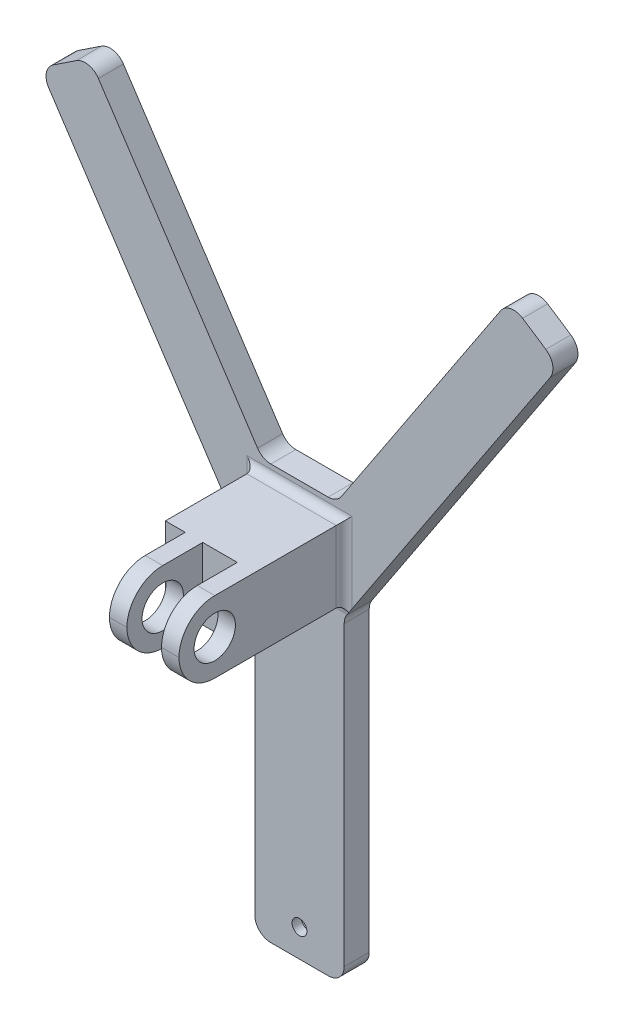
SolidWorks part; units mm, degrees
ref_plane "Plan de face" through (0, 0, 0) normal (0, 0, 1) x (1, 0, 0)
ref_plane "Plan de dessus" through (0, 0, 0) normal (0, 1, 0) x (1, 0, 0)
ref_plane "Plan de droite" through (0, 0, 0) normal (1, 0, 0) x (0, 0, -1)
sketch "Sketch1" plane through (0, 0, 0) normal (0, 0, 1) x (1, 0, 0)
  line L18 (-11.895, 65.5892) -> (11.895, 65.5892)
  line L19 (11.895, 65.5892) -> (67.0848, 148.9804)
  line L20 (67.0848, 148.9804) -> (82.9708, 138.4667)
  line L21 (82.9708, 138.4667) -> (14.2875, 34.687)
  line L23 (14.2875, 34.687) -> (14.2875, -66.913)
  line L24 (14.2875, -66.913) -> (-14.2875, -66.913)
  line L25 (-14.2875, -66.913) -> (-14.2875, 34.687)
  line L26 (-14.2875, 34.687) -> (-82.9708, 138.4667)
  line L27 (-82.9708, 138.4667) -> (-67.0848, 148.9804)
  line L28 (-67.0848, 148.9804) -> (-11.895, 65.5892)
  line L29 (-14.2875, 34.687) -> (14.2875, 34.687) construction
  point P2 (0, 34.687)
  point P12 (0, 65.5892)
  dimension "D1" = 28.575
  dimension "D2" = 19.05
  dimension "D3" = 100
  dimension "D4" = 100
  dimension "D5" = 101.6
extrude "Boss-Extrude1" add sketch "Sketch1" along normal blind 8
sketch "Sketch3" plane through (0, 0, 8) normal (0, 0, 1) x (1, 0, 0)
  line L0 (0, 65.5892) -> (0, 34.687) construction
  line L5 (14.2875, 38.7081) -> (-14.2875, 38.7081)
  line L6 (14.2875, 38.7081) -> (14.2875, 61.5681)
  line L7 (14.2875, 61.5681) -> (-14.2875, 61.5681)
  line L8 (-14.2875, 38.7081) -> (-14.2875, 61.5681)
  line L9 (14.2875, 38.7081) -> (-14.2875, 61.5681) construction
  line L10 (14.2875, 61.5681) -> (-14.2875, 38.7081) construction
  line L12 (11.895, 65.5892) -> (-11.895, 65.5892) construction
  point P0 (0, 50.1381)
  point P15 (0, 50.1381)
  dimension "D1" = 28.575
  dimension "D2" = 22.86
extrude "Boss-Extrude2" add sketch "Sketch3" along normal blind 52.8
sketch "Sketch6" plane through (0, 0, 8) normal (0, 0, 1) x (1, 0, 0)
  line L6 (-14.2875, 34.687) -> (-14.2875, -66.913) construction
  line L11 (-14.2875, 38.7081) -> (14.2875, 38.7081)
  line L12 (-14.2875, 38.7081) -> (-14.2875, -66.913)
  line L13 (-14.2875, -66.913) -> (14.2875, -66.913)
  line L14 (14.2875, 38.7081) -> (14.2875, -66.913)
  line L15 (-14.2875, -66.913) -> (14.2875, -66.913) construction
  line L16 (14.2875, -66.913) -> (14.2875, 34.687) construction
  line L17 (-14.2875, 38.7081) -> (14.2875, 38.7081) construction
extrude "Boss-Extrude3" [suppressed] add sketch "Sketch6" along normal blind 5.08
fillet "Fillet1" radius 5.08 10 edges at (-14.2875, -66.913, 4) (14.2875, -66.913, 4) (82.9708, 138.4667, 4) (67.0848, 148.9804, 4) (-67.0848, 148.9804, 4) (-82.9708, 138.4667, 4) (-11.895, 65.5892, 4) (11.895, 65.5892, 4) (14.2875, 34.687, 4) (-14.2875, 34.687, 4)
sketch "Sketch4" plane through (0, 38.7081, 0) normal (0, -1, 0) x (1, 0, 0)
  line L0 (-14.2875, 60.8) -> (14.2875, 60.8) construction
  line L1 (-14.2875, 60.8) -> (-7.9375, 60.8)
  line L2 (-14.2875, 60.8) -> (-14.2875, 36.575)
  line L3 (-14.2875, 36.575) -> (-7.9375, 36.575)
  line L4 (-7.9375, 60.8) -> (-7.9375, 36.575)
  line L5 (-2.3495, 60.8) -> (8.6995, 60.8)
  line L6 (-2.3495, 60.8) -> (-2.3495, 36.575)
  line L7 (-2.3495, 36.575) -> (8.6995, 36.575)
  line L8 (8.6995, 60.8) -> (8.6995, 36.575)
  line L9 (14.2875, 60.8) -> (14.2875, 8) construction
  dimension "D1" = 5.588
  dimension "D2" = 5.588
  dimension "D3" = 24.225
  dimension "D4" = 24.225
  dimension "D5" = 6.35
extrude "Cut-Extrude1" cut sketch "Sketch4" against normal through all
fillet "Fillet3" radius 11.43 4 edges at (11.4935, 61.5681, 60.8) (-5.1435, 61.5681, 60.8) (11.4935, 38.7081, 60.8) (-5.1435, 38.7081, 60.8)
sketch "Sketch5" plane through (-7.9375, 0, 0) normal (-1, 0, 0) x (0, 0, 1)
  circle A0 centre (49.37, 50.1381) radius 6.604
  dimension "D1" = 13.208
extrude "Cut-Extrude2" cut sketch "Sketch5" against normal through all
fillet "Fillet6" [suppressed] radius 2.54
sketch "Sketch7" plane through (0, 0, 0) normal (0, 0, -1) x (-1, 0, 0)
  line L0 (9.2075, -66.913) -> (-9.2075, -66.913) construction
  line L1 (14.2875, 33.1582) -> (14.2875, -61.833) construction
  circle A0 centre (0, -58.023) radius 4.2333
  dimension "D1" = 8.4667
  dimension "D2" = 8.89
  dimension "D3" = 14.2875
extrude "Cut-Extrude3" cut sketch "Sketch7" against normal blind 5.08
sketch "Sketch8" plane through (0, 0, 5.08) normal (0, 0, -1) x (-1, 0, 0)
  line L0 (14.2875, 33.1582) -> (14.2875, -61.833) construction
  line L2 (9.2075, -66.913) -> (-9.2075, -66.913) construction
  circle A0 centre (0, -58.023) radius 2.3812
  dimension "D1" = 4.7625
  dimension "D2" = 14.2875
  dimension "D3" = 8.89
extrude "Cut-Extrude4" cut sketch "Sketch8" against normal through all
fillet "Fillet7" radius 2.54 4 edges at (-14.2875, 50.1381, 8) (0, 61.5681, 8) (14.2875, 50.1381, 8) (0, 38.7081, 8)
